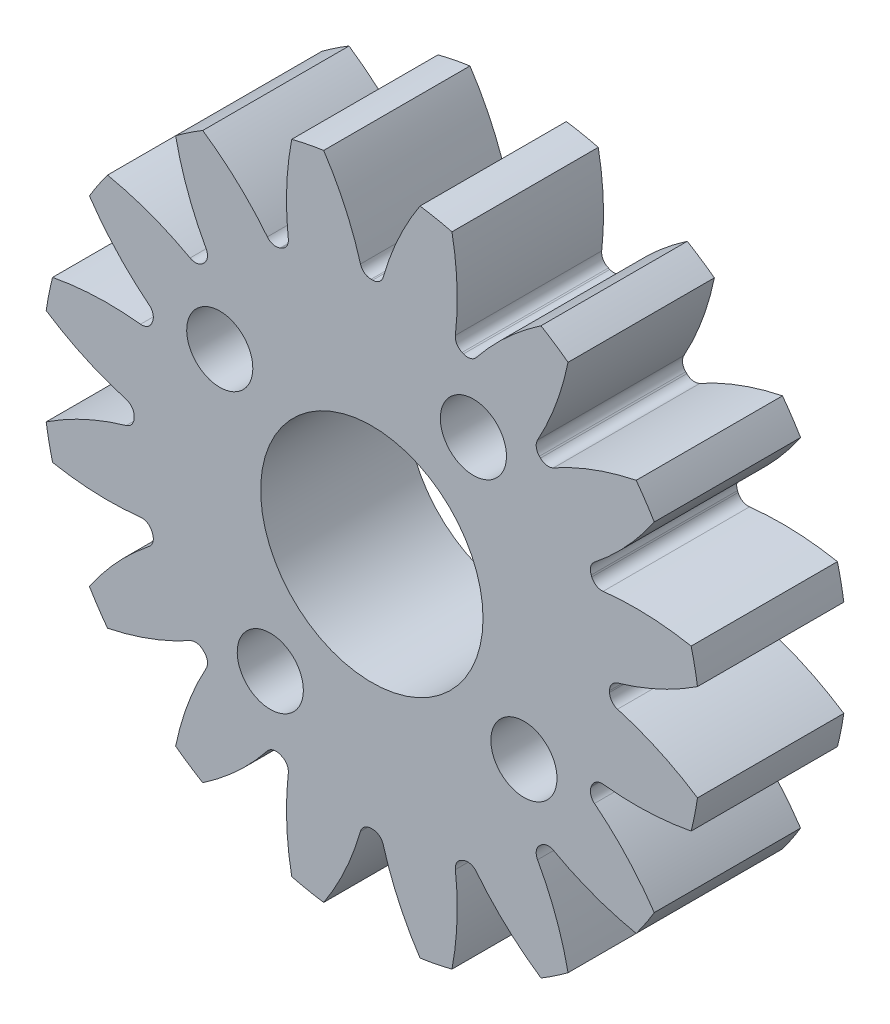
SolidWorks part; units mm, degrees
ref_plane "Front Plane" through (0, 0, 0) normal (0, 0, 1) x (1, 0, 0)
ref_plane "Top Plane" through (0, 0, 0) normal (0, 1, 0) x (1, 0, 0)
ref_plane "Right Plane" through (0, 0, 0) normal (1, 0, 0) x (0, 0, -1)
sketch "Sketch1" plane through (0, 0, 0) normal (0, 0, 1) x (1, 0, 0)
  line L0 (-203.2, 0) -> (203.2, 0) construction
  circle A0 centre (0, 0) radius 14.2875 construction
  circle A1 centre (0, 0) radius 12.7 construction
  circle A2 centre (0, 0) radius 10.3187 construction
  circle A3 centre (0, 0) radius 10.3251 construction
  circle A4 centre (0, 0) radius 6.35 construction
  circle A5 centre (0, 0) radius 10.3187 construction
  dimension "D2" = 1.5875
  dimension "D3" = 3.9688
  dimension "D1" = 3.9688
sketch "Sketch2" plane through (0, 0, 0) normal (1, 0, 0) x (0, 0, -1)
  line L0 (0, 0) -> (-19.05, 0) construction
  line L1 (-19.05, 0) -> (-31.75, 0) construction
  dimension "Overall Width" = 31.75
  dimension "Face Width" = 19.05
sketch "Sketch4" plane through (0, 0, 0) normal (1, 0, 0) x (0, 0, -1)
  line L0 (-31.75, 6.35) -> (-31.75, 10.3251)
  line L1 (-31.75, 10.3251) -> (-19.05, 10.3251)
  line L2 (-19.05, 10.3251) -> (-19.05, 14.2875)
  line L3 (-19.05, 14.2875) -> (0, 14.2875)
  line L4 (0, 14.2875) -> (0, 6.35)
  line L5 (-19.05, 10.3251) -> (-19.05, 0) construction
  line L6 (0, 14.2875) -> (0, -14.2875) construction
  line L7 (-19.05, 10.3251) -> (0, 10.3251) construction
  line L12 (-31.75, 6.35) -> (0, 6.35)
revolve "Revolve1" add sketch "Sketch4" angle 360 about L1
fillet "Fillet2" radius 0.2858 4 edges at (0, 10.3251, 31.75) (0, 10.3251, 19.05) (0, 14.2875, 19.05) (0, 14.2875, 0)
sketch "Sketch7" plane through (0, 0, 19.05) normal (0, 0, 1) x (1, 0, 0)
  line L0 (0, 0) -> (0, 14.2875) construction
  line L1 (1.2448, 12.6388) -> (1.9701, 14.151) construction
  line L3 (2.7874, 14.013) -> (2.4776, 12.456) construction
  line L4 (2.4776, 12.456) -> (2.0131, 10.1205) construction
  line L5 (0, 0) -> (2.0131, 10.1205) construction
  line L6 (1.2448, 12.6388) -> (0, 0) construction
  line L7 (1.2448, 12.6388) -> (1.4004, 14.2187) construction
  line L8 (1.2448, 12.6388) -> (0, 0) construction
  circle A0 centre (0, 0) radius 14.2875 construction
  arc A1 (-0.0331, 10.3187) -> (0.0331, 10.3187) centre (0, 0) cw
  circle A2 centre (0, 0) radius 10.3187 construction
  arc A3 (-1.2448, 12.6388) -> (1.2448, 12.6388) centre (0, 0) cw construction
  circle A4 centre (0, 0) radius 12.7 construction
  arc A5 (3.4772, 13.8579) -> (2.0907, 14.1337) centre (0, 0) ccw construction
  arc A6 (1.2448, 12.6388) -> (3.6866, 12.1531) centre (0, 0) cw construction
  arc A7 (-2.0907, 14.1337) -> (2.0907, 14.1337) centre (0, 0) cw
  arc A8 (0.4923, 10.6631) -> (2.0907, 14.1337) centre (12.6957, 7.1464) cw
  arc A9 (-0.4923, 10.6631) -> (-2.0907, 14.1337) centre (-12.6957, 7.1464) ccw
  arc A10 (-0.0331, 10.3187) -> (-0.4923, 10.6631) centre (-0.0346, 10.795) cw
  arc A11 (0.0331, 10.3187) -> (0.4923, 10.6631) centre (0.0346, 10.795) ccw
  point P26 (-0.3963, 10.3111)
  point P29 (0.3963, 10.3111)
  dimension "D4" = 0.4763
  dimension "D5" = 12.7
  dimension "D3" = 20
  dimension "D1" = 4.9873
  dimension "D2" = 2.4936
extrude "Cut-Extrude2" cut sketch "Sketch7" against normal through all
pattern_circular "CirPattern1" count 16 over 360 about axis through (0, 0, 31.75) along (0, 0, -1) of "Cut-Extrude2"
sketch "Sketch9" [suppressed] plane through (0, 0, 0) normal (0, 0, 1) x (1, 0, 0)
  circle A0 centre (0, 0) radius 10.3187 construction
  circle A1 centre (0, 0) radius 10.3187
ref_plane "Plane1" through (0, 0, 0) normal (0, 0, -1) x (-1, 0, 0)
ref_plane "Plane2" through (0, 0, 31.75) normal (0, 0, 1) x (1, 0, 0)
sketch "Sketch10" plane through (0, 0, 31.75) normal (0, 0, 1) x (1, 0, 0)
  circle A0 centre (0, 0) radius 29.0934
extrude "Cut-Extrude3" cut sketch "Sketch10" against normal blind 15.24
sketch "Sketch11" plane through (0, 0, 0) normal (0, 0, -1) x (-1, 0, 0)
  circle A0 centre (0, 0) radius 20.5552
extrude "Cut-Extrude4" cut sketch "Sketch11" against normal blind 10.16
sketch "Sketch12" plane through (0, 0, 16.51) normal (0, 0, 1) x (1, 0, 0)
  circle A0 centre (0, 0) radius 7.9171
  circle A1 centre (0, 0) radius 4.826
  dimension "D1" = 9.652
extrude "Boss-Extrude1" add sketch "Sketch12" against normal up to surface (6.35 mm away) up to face at (0, 6.35, 10.16)
sketch "Эскиз1" plane through (0, 0, 0) normal (0, 0, -1) x (-1, 0, 0)
  line L0 (0, 0) -> (17.9765, 12.0041) construction
  circle A0 centre (6.601, 4.408) radius 1.4351
  circle A1 centre (4.408, -6.601) radius 1.4351
  circle A2 centre (-6.601, -4.408) radius 1.4351
  circle A3 centre (-4.408, 6.601) radius 1.4351
  dimension "D3" = 2.8702
  dimension "D2" = 7.9375
  dimension "D1" = 4
extrude "Вырез-Вытянуть1" cut sketch "Эскиз1" against normal through all
sketch "Sketch13" plane through (0, 0, 16.51) normal (0, 0, 1) x (1, 0, 0)
  circle A0 centre (-4.408, -6.601) radius 1.4351 construction
  circle A1 centre (-4.408, -6.601) radius 1.4351
  circle A2 centre (6.601, -4.408) radius 1.4351 construction
  circle A3 centre (4.408, 6.601) radius 1.4351 construction
  circle A4 centre (-6.601, 4.408) radius 1.4351 construction
  circle A5 centre (6.601, -4.408) radius 1.4351
  circle A6 centre (4.408, 6.601) radius 1.4351
  circle A7 centre (-6.601, 4.408) radius 1.4351
  circle A8 centre (0, 0) radius 4.826 construction
  circle A9 centre (0, 0) radius 4.826
  arc A96 (-7.3402, -12.2578) -> (-4.5354, -9.663) centre (-14.4641, -1.7439) ccw
  arc A97 (-3.9794, -9.5206) -> (-4.5354, -9.663) centre (-4.1631, -9.96) ccw
  arc A98 (-3.9794, -9.5206) -> (-3.9182, -9.5459) centre (0, 0) ccw
  arc A99 (-3.6258, -10.0398) -> (-3.9182, -9.5459) centre (-4.099, -9.9865) ccw
  arc A100 (-3.6258, -10.0398) -> (-3.4772, -13.8579) centre (8.9945, -11.4608) ccw
  arc A101 (-3.4772, -13.8579) -> (-2.0907, -14.1337) centre (0, 0) ccw
  arc A102 (-2.0907, -14.1337) -> (-0.4923, -10.6631) centre (-12.6957, -7.1464) ccw
  arc A103 (-0.0331, -10.3187) -> (-0.4923, -10.6631) centre (-0.0346, -10.795) ccw
  arc A104 (-0.0331, -10.3187) -> (0.0331, -10.3187) centre (0, 0) ccw
  arc A105 (0.4923, -10.6631) -> (0.0331, -10.3187) centre (0.0346, -10.795) ccw
  arc A106 (0.4923, -10.6631) -> (2.0907, -14.1337) centre (12.6957, -7.1464) ccw
  arc A107 (2.0907, -14.1337) -> (3.4772, -13.8579) centre (0, 0) ccw
  arc A108 (3.4772, -13.8579) -> (3.6258, -10.0398) centre (-8.9945, -11.4608) ccw
  arc A109 (3.9182, -9.5459) -> (3.6258, -10.0398) centre (4.099, -9.9865) ccw
  arc A110 (3.9182, -9.5459) -> (3.9794, -9.5206) centre (0, 0) ccw
  arc A111 (4.5354, -9.663) -> (3.9794, -9.5206) centre (4.1631, -9.96) ccw
  arc A112 (4.5354, -9.663) -> (7.3402, -12.2578) centre (14.4641, -1.7439) ccw
  arc A113 (7.3402, -12.2578) -> (8.5157, -11.4724) centre (0, 0) ccw
  arc A114 (8.5157, -11.4724) -> (7.1918, -7.8881) centre (-3.924, -14.0305) ccw
  arc A115 (7.273, -7.3198) -> (7.1918, -7.8881) centre (7.6087, -7.6577) ccw
  arc A116 (7.273, -7.3198) -> (7.3198, -7.273) centre (0, 0) ccw
  arc A117 (7.8881, -7.1918) -> (7.3198, -7.273) centre (7.6577, -7.6087) ccw
  arc A118 (7.8881, -7.1918) -> (11.4724, -8.5157) centre (14.0305, 3.924) ccw
  arc A119 (11.4724, -8.5157) -> (12.2578, -7.3402) centre (0, 0) ccw
  arc A120 (12.2578, -7.3402) -> (9.663, -4.5354) centre (1.7439, -14.4641) ccw
  arc A121 (9.5206, -3.9794) -> (9.663, -4.5354) centre (9.96, -4.1631) ccw
  arc A122 (9.5206, -3.9794) -> (9.5459, -3.9182) centre (0, 0) ccw
  arc A123 (10.0398, -3.6258) -> (9.5459, -3.9182) centre (9.9865, -4.099) ccw
  arc A124 (10.0398, -3.6258) -> (13.8579, -3.4772) centre (11.4608, 8.9945) ccw
  arc A125 (13.8579, -3.4772) -> (14.1337, -2.0907) centre (0, 0) ccw
  arc A126 (14.1337, -2.0907) -> (10.6631, -0.4923) centre (7.1464, -12.6957) ccw
  arc A127 (10.3187, -0.0331) -> (10.6631, -0.4923) centre (10.795, -0.0346) ccw
  arc A128 (10.3187, -0.0331) -> (10.3187, 0.0331) centre (0, 0) ccw
  arc A129 (10.6631, 0.4923) -> (10.3187, 0.0331) centre (10.795, 0.0346) ccw
  arc A130 (10.6631, 0.4923) -> (14.1337, 2.0907) centre (7.1464, 12.6957) ccw
  arc A131 (14.1337, 2.0907) -> (13.8579, 3.4772) centre (0, 0) ccw
  arc A132 (13.8579, 3.4772) -> (10.0398, 3.6258) centre (11.4608, -8.9945) ccw
  arc A133 (9.5459, 3.9182) -> (10.0398, 3.6258) centre (9.9865, 4.099) ccw
  arc A134 (9.5459, 3.9182) -> (9.5206, 3.9794) centre (0, 0) ccw
  arc A135 (9.663, 4.5354) -> (9.5206, 3.9794) centre (9.96, 4.1631) ccw
  arc A136 (9.663, 4.5354) -> (12.2578, 7.3402) centre (1.7439, 14.4641) ccw
  arc A137 (12.2578, 7.3402) -> (11.4724, 8.5157) centre (0, 0) ccw
  arc A138 (11.4724, 8.5157) -> (7.8881, 7.1918) centre (14.0305, -3.924) ccw
  arc A139 (7.3198, 7.273) -> (7.8881, 7.1918) centre (7.6577, 7.6087) ccw
  arc A140 (7.3198, 7.273) -> (7.273, 7.3198) centre (0, 0) ccw
  arc A141 (7.1918, 7.8881) -> (7.273, 7.3198) centre (7.6087, 7.6577) ccw
  arc A142 (7.1918, 7.8881) -> (8.5157, 11.4724) centre (-3.924, 14.0305) ccw
  arc A143 (8.5157, 11.4724) -> (7.3402, 12.2578) centre (0, 0) ccw
  arc A144 (7.3402, 12.2578) -> (4.5354, 9.663) centre (14.4641, 1.7439) ccw
  arc A145 (3.9794, 9.5206) -> (4.5354, 9.663) centre (4.1631, 9.96) ccw
  arc A146 (3.9794, 9.5206) -> (3.9182, 9.5459) centre (0, 0) ccw
  arc A147 (3.6258, 10.0398) -> (3.9182, 9.5459) centre (4.099, 9.9865) ccw
  arc A148 (3.6258, 10.0398) -> (3.4772, 13.8579) centre (-8.9945, 11.4608) ccw
  arc A149 (3.4772, 13.8579) -> (2.0907, 14.1337) centre (0, 0) ccw
  arc A150 (2.0907, 14.1337) -> (0.4923, 10.6631) centre (12.6957, 7.1464) ccw
  arc A151 (0.0331, 10.3187) -> (0.4923, 10.6631) centre (0.0346, 10.795) ccw
  arc A152 (0.0331, 10.3187) -> (-0.0331, 10.3187) centre (0, 0) ccw
  arc A153 (-0.4923, 10.6631) -> (-0.0331, 10.3187) centre (-0.0346, 10.795) ccw
  arc A154 (-0.4923, 10.6631) -> (-2.0907, 14.1337) centre (-12.6957, 7.1464) ccw
  arc A155 (-2.0907, 14.1337) -> (-3.4772, 13.8579) centre (0, 0) ccw
  arc A156 (-3.4772, 13.8579) -> (-3.6258, 10.0398) centre (8.9945, 11.4608) ccw
  arc A157 (-3.9182, 9.5459) -> (-3.6258, 10.0398) centre (-4.099, 9.9865) ccw
  arc A158 (-3.9182, 9.5459) -> (-3.9794, 9.5206) centre (0, 0) ccw
  arc A159 (-4.5354, 9.663) -> (-3.9794, 9.5206) centre (-4.1631, 9.96) ccw
  arc A160 (-4.5354, 9.663) -> (-7.3402, 12.2578) centre (-14.4641, 1.7439) ccw
  arc A161 (-7.3402, 12.2578) -> (-8.5157, 11.4724) centre (0, 0) ccw
  arc A162 (-8.5157, 11.4724) -> (-7.1918, 7.8881) centre (3.924, 14.0305) ccw
  arc A163 (-7.273, 7.3198) -> (-7.1918, 7.8881) centre (-7.6087, 7.6577) ccw
  arc A164 (-7.273, 7.3198) -> (-7.3198, 7.273) centre (0, 0) ccw
  arc A165 (-7.8881, 7.1918) -> (-7.3198, 7.273) centre (-7.6577, 7.6087) ccw
  arc A166 (-7.8881, 7.1918) -> (-11.4724, 8.5157) centre (-14.0305, -3.924) ccw
  arc A167 (-11.4724, 8.5157) -> (-12.2578, 7.3402) centre (0, 0) ccw
  arc A168 (-12.2578, 7.3402) -> (-9.663, 4.5354) centre (-1.7439, 14.4641) ccw
  arc A169 (-9.5206, 3.9794) -> (-9.663, 4.5354) centre (-9.96, 4.1631) ccw
  arc A170 (-9.5206, 3.9794) -> (-9.5459, 3.9182) centre (0, 0) ccw
  arc A171 (-10.0398, 3.6258) -> (-9.5459, 3.9182) centre (-9.9865, 4.099) ccw
  arc A172 (-10.0398, 3.6258) -> (-13.8579, 3.4772) centre (-11.4608, -8.9945) ccw
  arc A173 (-13.8579, 3.4772) -> (-14.1337, 2.0907) centre (0, 0) ccw
  arc A174 (-14.1337, 2.0907) -> (-10.6631, 0.4923) centre (-7.1464, 12.6957) ccw
  arc A175 (-10.3187, 0.0331) -> (-10.6631, 0.4923) centre (-10.795, 0.0346) ccw
  arc A176 (-10.3187, 0.0331) -> (-10.3187, -0.0331) centre (0, 0) ccw
  arc A177 (-10.6631, -0.4923) -> (-10.3187, -0.0331) centre (-10.795, -0.0346) ccw
  arc A178 (-10.6631, -0.4923) -> (-14.1337, -2.0907) centre (-7.1464, -12.6957) ccw
  arc A179 (-14.1337, -2.0907) -> (-13.8579, -3.4772) centre (0, 0) ccw
  arc A180 (-13.8579, -3.4772) -> (-10.0398, -3.6258) centre (-11.4608, 8.9945) ccw
  arc A181 (-9.5459, -3.9182) -> (-10.0398, -3.6258) centre (-9.9865, -4.099) ccw
  arc A182 (-9.5459, -3.9182) -> (-9.5206, -3.9794) centre (0, 0) ccw
  arc A183 (-9.663, -4.5354) -> (-9.5206, -3.9794) centre (-9.96, -4.1631) ccw
  arc A184 (-9.663, -4.5354) -> (-12.2578, -7.3402) centre (-1.7439, -14.4641) ccw
  arc A185 (-12.2578, -7.3402) -> (-11.4724, -8.5157) centre (0, 0) ccw
  arc A186 (-11.4724, -8.5157) -> (-7.8881, -7.1918) centre (-14.0305, 3.924) ccw
  arc A187 (-7.3198, -7.273) -> (-7.8881, -7.1918) centre (-7.6577, -7.6087) ccw
  arc A188 (-7.3198, -7.273) -> (-7.273, -7.3198) centre (0, 0) ccw
  arc A189 (-7.1918, -7.8881) -> (-7.273, -7.3198) centre (-7.6087, -7.6577) ccw
  arc A190 (-7.1918, -7.8881) -> (-8.5157, -11.4724) centre (3.924, -14.0305) ccw
  arc A191 (-8.5157, -11.4724) -> (-7.3402, -12.2578) centre (0, 0) ccw
  arc A192 (-7.3402, -12.2578) -> (-4.5354, -9.663) centre (-14.4641, -1.7439) ccw
  arc A193 (-3.9794, -9.5206) -> (-4.5354, -9.663) centre (-4.1631, -9.96) ccw
  arc A194 (-3.9794, -9.5206) -> (-3.9182, -9.5459) centre (0, 0) ccw
  arc A195 (-3.6258, -10.0398) -> (-3.9182, -9.5459) centre (-4.099, -9.9865) ccw
  arc A196 (-3.6258, -10.0398) -> (-3.4772, -13.8579) centre (8.9945, -11.4608) ccw
  arc A197 (-3.4772, -13.8579) -> (-2.0907, -14.1337) centre (0, 0) ccw
  arc A198 (-2.0907, -14.1337) -> (-0.4923, -10.6631) centre (-12.6957, -7.1464) ccw
  arc A199 (-0.0331, -10.3187) -> (-0.4923, -10.6631) centre (-0.0346, -10.795) ccw
  arc A200 (-0.0331, -10.3187) -> (0.0331, -10.3187) centre (0, 0) ccw
  arc A201 (0.4923, -10.6631) -> (0.0331, -10.3187) centre (0.0346, -10.795) ccw
  arc A202 (0.4923, -10.6631) -> (2.0907, -14.1337) centre (12.6957, -7.1464) ccw
  arc A203 (2.0907, -14.1337) -> (3.4772, -13.8579) centre (0, 0) ccw
  arc A204 (3.4772, -13.8579) -> (3.6258, -10.0398) centre (-8.9945, -11.4608) ccw
  arc A205 (3.9182, -9.5459) -> (3.6258, -10.0398) centre (4.099, -9.9865) ccw
  arc A206 (3.9182, -9.5459) -> (3.9794, -9.5206) centre (0, 0) ccw
  arc A207 (4.5354, -9.663) -> (3.9794, -9.5206) centre (4.1631, -9.96) ccw
  arc A208 (4.5354, -9.663) -> (7.3402, -12.2578) centre (14.4641, -1.7439) ccw
  arc A209 (7.3402, -12.2578) -> (8.5157, -11.4724) centre (0, 0) ccw
  arc A210 (8.5157, -11.4724) -> (7.1918, -7.8881) centre (-3.924, -14.0305) ccw
  arc A211 (7.273, -7.3198) -> (7.1918, -7.8881) centre (7.6087, -7.6577) ccw
  arc A212 (7.273, -7.3198) -> (7.3198, -7.273) centre (0, 0) ccw
  arc A213 (7.8881, -7.1918) -> (7.3198, -7.273) centre (7.6577, -7.6087) ccw
  arc A214 (7.8881, -7.1918) -> (11.4724, -8.5157) centre (14.0305, 3.924) ccw
  arc A215 (11.4724, -8.5157) -> (12.2578, -7.3402) centre (0, 0) ccw
  arc A216 (12.2578, -7.3402) -> (9.663, -4.5354) centre (1.7439, -14.4641) ccw
  arc A217 (9.5206, -3.9794) -> (9.663, -4.5354) centre (9.96, -4.1631) ccw
  arc A218 (9.5206, -3.9794) -> (9.5459, -3.9182) centre (0, 0) ccw
  arc A219 (10.0398, -3.6258) -> (9.5459, -3.9182) centre (9.9865, -4.099) ccw
  arc A220 (10.0398, -3.6258) -> (13.8579, -3.4772) centre (11.4608, 8.9945) ccw
  arc A221 (13.8579, -3.4772) -> (14.1337, -2.0907) centre (0, 0) ccw
  arc A222 (14.1337, -2.0907) -> (10.6631, -0.4923) centre (7.1464, -12.6957) ccw
  arc A223 (10.3187, -0.0331) -> (10.6631, -0.4923) centre (10.795, -0.0346) ccw
  arc A224 (10.3187, -0.0331) -> (10.3187, 0.0331) centre (0, 0) ccw
  arc A225 (10.6631, 0.4923) -> (10.3187, 0.0331) centre (10.795, 0.0346) ccw
  arc A226 (10.6631, 0.4923) -> (14.1337, 2.0907) centre (7.1464, 12.6957) ccw
  arc A227 (14.1337, 2.0907) -> (13.8579, 3.4772) centre (0, 0) ccw
  arc A228 (13.8579, 3.4772) -> (10.0398, 3.6258) centre (11.4608, -8.9945) ccw
  arc A229 (9.5459, 3.9182) -> (10.0398, 3.6258) centre (9.9865, 4.099) ccw
  arc A230 (9.5459, 3.9182) -> (9.5206, 3.9794) centre (0, 0) ccw
  arc A231 (9.663, 4.5354) -> (9.5206, 3.9794) centre (9.96, 4.1631) ccw
  arc A232 (9.663, 4.5354) -> (12.2578, 7.3402) centre (1.7439, 14.4641) ccw
  arc A233 (12.2578, 7.3402) -> (11.4724, 8.5157) centre (0, 0) ccw
  arc A234 (11.4724, 8.5157) -> (7.8881, 7.1918) centre (14.0305, -3.924) ccw
  arc A235 (7.3198, 7.273) -> (7.8881, 7.1918) centre (7.6577, 7.6087) ccw
  arc A236 (7.3198, 7.273) -> (7.273, 7.3198) centre (0, 0) ccw
  arc A237 (7.1918, 7.8881) -> (7.273, 7.3198) centre (7.6087, 7.6577) ccw
  arc A238 (7.1918, 7.8881) -> (8.5157, 11.4724) centre (-3.924, 14.0305) ccw
  arc A239 (8.5157, 11.4724) -> (7.3402, 12.2578) centre (0, 0) ccw
  arc A240 (7.3402, 12.2578) -> (4.5354, 9.663) centre (14.4641, 1.7439) ccw
  arc A241 (3.9794, 9.5206) -> (4.5354, 9.663) centre (4.1631, 9.96) ccw
  arc A242 (3.9794, 9.5206) -> (3.9182, 9.5459) centre (0, 0) ccw
  arc A243 (3.6258, 10.0398) -> (3.9182, 9.5459) centre (4.099, 9.9865) ccw
  arc A244 (3.6258, 10.0398) -> (3.4772, 13.8579) centre (-8.9945, 11.4608) ccw
  arc A245 (3.4772, 13.8579) -> (2.0907, 14.1337) centre (0, 0) ccw
  arc A246 (2.0907, 14.1337) -> (0.4923, 10.6631) centre (12.6957, 7.1464) ccw
  arc A247 (0.0331, 10.3187) -> (0.4923, 10.6631) centre (0.0346, 10.795) ccw
  arc A248 (0.0331, 10.3187) -> (-0.0331, 10.3187) centre (0, 0) ccw
  arc A249 (-0.4923, 10.6631) -> (-0.0331, 10.3187) centre (-0.0346, 10.795) ccw
  arc A250 (-0.4923, 10.6631) -> (-2.0907, 14.1337) centre (-12.6957, 7.1464) ccw
  arc A251 (-2.0907, 14.1337) -> (-3.4772, 13.8579) centre (0, 0) ccw
  arc A252 (-3.4772, 13.8579) -> (-3.6258, 10.0398) centre (8.9945, 11.4608) ccw
  arc A253 (-3.9182, 9.5459) -> (-3.6258, 10.0398) centre (-4.099, 9.9865) ccw
  arc A254 (-3.9182, 9.5459) -> (-3.9794, 9.5206) centre (0, 0) ccw
  arc A255 (-4.5354, 9.663) -> (-3.9794, 9.5206) centre (-4.1631, 9.96) ccw
  arc A256 (-4.5354, 9.663) -> (-7.3402, 12.2578) centre (-14.4641, 1.7439) ccw
  arc A257 (-7.3402, 12.2578) -> (-8.5157, 11.4724) centre (0, 0) ccw
  arc A258 (-8.5157, 11.4724) -> (-7.1918, 7.8881) centre (3.924, 14.0305) ccw
  arc A259 (-7.273, 7.3198) -> (-7.1918, 7.8881) centre (-7.6087, 7.6577) ccw
  arc A260 (-7.273, 7.3198) -> (-7.3198, 7.273) centre (0, 0) ccw
  arc A261 (-7.8881, 7.1918) -> (-7.3198, 7.273) centre (-7.6577, 7.6087) ccw
  arc A262 (-7.8881, 7.1918) -> (-11.4724, 8.5157) centre (-14.0305, -3.924) ccw
  arc A263 (-11.4724, 8.5157) -> (-12.2578, 7.3402) centre (0, 0) ccw
  arc A264 (-12.2578, 7.3402) -> (-9.663, 4.5354) centre (-1.7439, 14.4641) ccw
  arc A265 (-9.5206, 3.9794) -> (-9.663, 4.5354) centre (-9.96, 4.1631) ccw
  arc A266 (-9.5206, 3.9794) -> (-9.5459, 3.9182) centre (0, 0) ccw
  arc A267 (-10.0398, 3.6258) -> (-9.5459, 3.9182) centre (-9.9865, 4.099) ccw
  arc A268 (-10.0398, 3.6258) -> (-13.8579, 3.4772) centre (-11.4608, -8.9945) ccw
  arc A269 (-13.8579, 3.4772) -> (-14.1337, 2.0907) centre (0, 0) ccw
  arc A270 (-14.1337, 2.0907) -> (-10.6631, 0.4923) centre (-7.1464, 12.6957) ccw
  arc A271 (-10.3187, 0.0331) -> (-10.6631, 0.4923) centre (-10.795, 0.0346) ccw
  arc A272 (-10.3187, 0.0331) -> (-10.3187, -0.0331) centre (0, 0) ccw
  arc A273 (-10.6631, -0.4923) -> (-10.3187, -0.0331) centre (-10.795, -0.0346) ccw
  arc A274 (-10.6631, -0.4923) -> (-14.1337, -2.0907) centre (-7.1464, -12.6957) ccw
  arc A275 (-14.1337, -2.0907) -> (-13.8579, -3.4772) centre (0, 0) ccw
  arc A276 (-13.8579, -3.4772) -> (-10.0398, -3.6258) centre (-11.4608, 8.9945) ccw
  arc A277 (-9.5459, -3.9182) -> (-10.0398, -3.6258) centre (-9.9865, -4.099) ccw
  arc A278 (-9.5459, -3.9182) -> (-9.5206, -3.9794) centre (0, 0) ccw
  arc A279 (-9.663, -4.5354) -> (-9.5206, -3.9794) centre (-9.96, -4.1631) ccw
  arc A280 (-9.663, -4.5354) -> (-12.2578, -7.3402) centre (-1.7439, -14.4641) ccw
  arc A281 (-12.2578, -7.3402) -> (-11.4724, -8.5157) centre (0, 0) ccw
  arc A282 (-11.4724, -8.5157) -> (-7.8881, -7.1918) centre (-14.0305, 3.924) ccw
  arc A283 (-7.3198, -7.273) -> (-7.8881, -7.1918) centre (-7.6577, -7.6087) ccw
  arc A284 (-7.3198, -7.273) -> (-7.273, -7.3198) centre (0, 0) ccw
  arc A285 (-7.1918, -7.8881) -> (-7.273, -7.3198) centre (-7.6087, -7.6577) ccw
  arc A286 (-7.1918, -7.8881) -> (-8.5157, -11.4724) centre (3.924, -14.0305) ccw
  arc A287 (-8.5157, -11.4724) -> (-7.3402, -12.2578) centre (0, 0) ccw
  dimension "D1" = 0
equation "\"D1@Sketch1\"=2.5*(\"Pitch Dia.@Sketch1\"/\"Number of Teeth@Sketch1\")"
equation "\"D1@CirPattern1\"=\"Number of Teeth@Sketch1\""
equation "\"D1@Fillet2\"=\"OD@Sketch1\"*.01"
equation "\"D1@Sketch7\"=3.14159*(\"Pitch Dia.@Sketch1\"/\"Number of Teeth@Sketch1\")"
equation "\"D2@Sketch7\"=\"D1@Sketch7\"/2"
equation "\"D4@Sketch7\"=\"D1@Sketch7\"*.0955"
equation "\"D5@Sketch7\"=\"Pitch Dia.@Sketch1\"/2"
